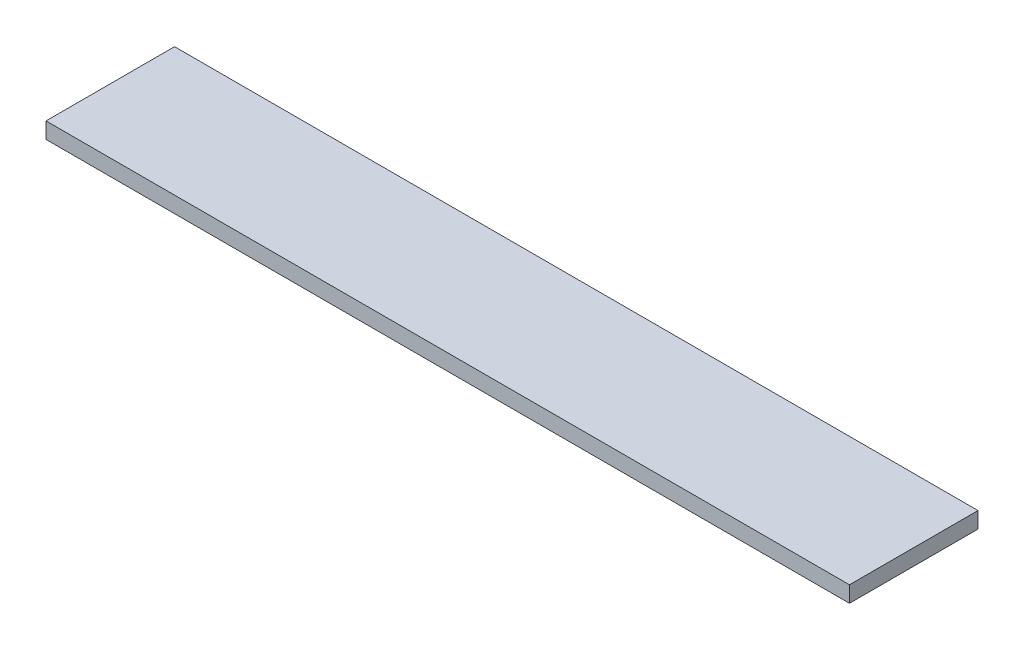
SolidWorks part; units mm, degrees
material "6061-T6 (SS)"
ref_plane "Front" through (0, 0, 0) normal (0, 0, 1) x (1, 0, 0)
ref_plane "Top" through (0, 0, 0) normal (0, 1, 0) x (1, 0, 0)
ref_plane "Right" through (0, 0, 0) normal (1, 0, 0) x (0, 0, -1)
sketch "Sketch1" plane through (0, 0, 0) normal (0, 1, 0) x (1, 0, 0)
  line L0 (317.5, 0) -> (317.5, 50.8) construction
  line L1 (0, 0) -> (317.5, 0)
  line L2 (0, 0) -> (0, 50.8)
  line L3 (0, 50.8) -> (317.5, 50.8)
  line L4 (317.5, 0) -> (317.5, 50.8)
  dimension "D1" = 50.8
extrude "Boss-Extrude1" add sketch "Sketch1" along normal blind 6.35
